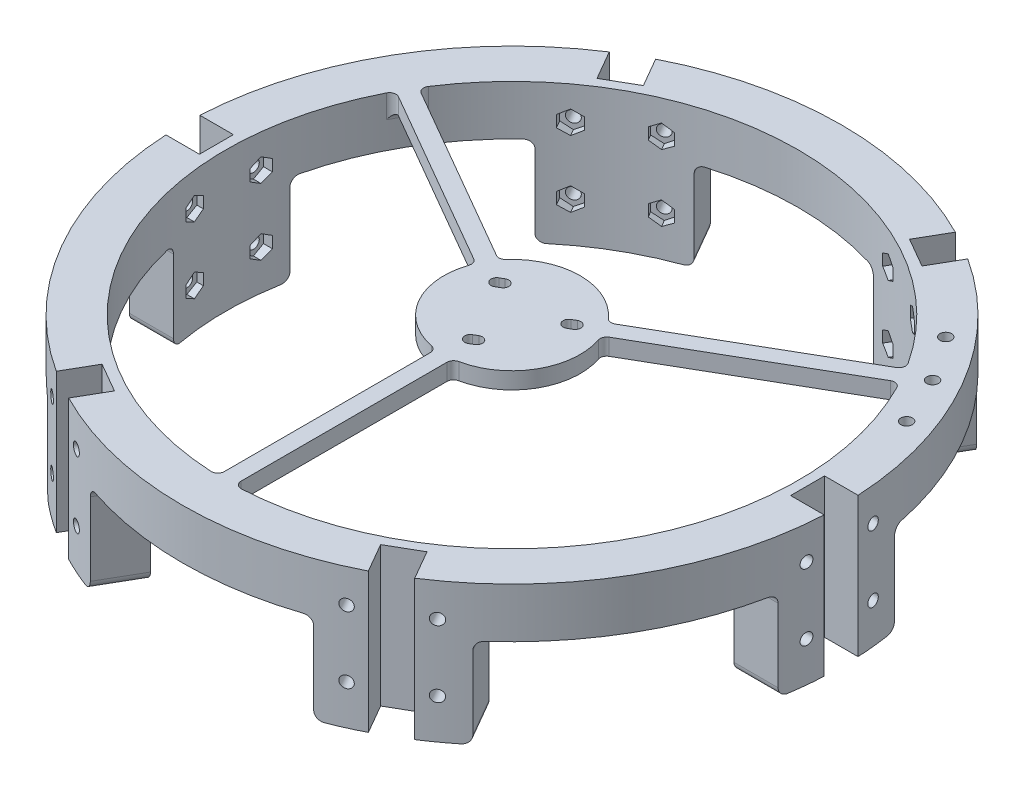
SolidWorks part; units mm, degrees
ref_plane "Спереди" through (0, 0, 0) normal (0, 0, 1) x (1, 0, 0)
ref_plane "Сверху" through (0, 0, 0) normal (0, 1, 0) x (1, 0, 0)
ref_plane "Справа" through (0, 0, 0) normal (1, 0, 0) x (0, 0, -1)
sketch "Эскиз1" plane through (0, 0, 0) normal (0, 1, 0) x (1, 0, 0)
  circle A0 centre (0, 0) radius 99
  dimension "D1" = 198
extrude "Бобышка-Вытянуть1" add sketch "Эскиз1" along normal blind 15
sketch "Эскиз2" plane through (0, 15, 0) normal (0, 1, 0) x (1, 0, 0)
  line L0 (-93.9, 0) -> (0, 0) construction
  line L1 (-99, 5.1) -> (-88.8, 5.1)
  line L2 (-99, 5.1) -> (-99, -5.1)
  line L3 (-99, -5.1) -> (-88.8, -5.1)
  line L4 (-88.8, 5.1) -> (-88.8, -5.1)
  line L5 (-99, 5.1) -> (-88.8, -5.1) construction
  line L6 (-99, -5.1) -> (-88.8, 5.1) construction
  circle A0 centre (0, 0) radius 99 construction
  point P0 (-93.9, 0)
  dimension "D1" = 10.2
  dimension "D2" = 10.2
extrude "Вырез-Вытянуть1" cut sketch "Эскиз2" against normal through all
pattern_circular "Круговой массив1" count 6 over 360 about axis through (0, 15, 0) along (0, 1, 0) of "Вырез-Вытянуть1"
sketch "Эскиз3" plane through (0, 15, 0) normal (0, 1, 0) x (1, 0, 0)
  circle A0 centre (0, 0) radius 86
  point P5 (-86, 0)
  dimension "D1" = 172
extrude "Вырез-Вытянуть2" cut sketch "Эскиз3" against normal through all
ref_plane "Плоскость1" through (0, 0, -99) normal (0, 0, -1) x (-1, 0, 0)
sketch "Эскиз6" plane through (0, 0, -99) normal (0, 0, -1) x (-1, 0, 0)
  line L0 (-45.0175, 0) -> (45.0175, 0) construction
  line L1 (-15, -17.9681) -> (15, -17.9681)
  line L2 (-15, -17.9681) -> (-15, 0)
  line L3 (-15, 0) -> (15, 0)
  line L4 (15, -17.9681) -> (15, 0)
  line L5 (-15, -17.9681) -> (15, 0) construction
  line L6 (-15, 0) -> (15, -17.9681) construction
  line L7 (0, -8.984) -> (0, 0) construction
  point P0 (0, -8.984)
  dimension "D1" = 30
sketch "Эскиз7" plane through (0, 15, 0) normal (0, 1, 0) x (1, 0, 0)
  circle A0 centre (0, 0) radius 99
  arc A1 (45.0175, 88.1727) -> (-45.0175, 88.1727) centre (0, 0) ccw construction
  circle A2 centre (0, 0) radius 104
  point P7 (0, 0)
  dimension "D1" = 5
sketch "Эскиз8" plane through (0, 0, -99) normal (0, 0, -1) x (-1, 0, 0)
  line L0 (0, -8.5) -> (0, 0) construction
  circle A0 centre (0, -8.5) radius 2.5
  dimension "D2" = 5
  dimension "D1" = 8.5
sketch "Эскиз10" plane through (0, 0, 0) normal (0, -1, 0) x (1, 0, 0)
  line L0 (67.0955, -65.2982) -> (88.5621, -32.8102)
  line L1 (88.5621, -32.8102) -> (81.0551, -27.8499)
  line L2 (81.0551, -27.8499) -> (59.5884, -60.3378)
  line L3 (59.5884, -60.3378) -> (67.0955, -65.2982)
extrude "Бобышка-Вытянуть3" add sketch "Эскиз10" along normal blind 500
sketch "Эскиз11" plane through (0, 15, 0) normal (0, 1, 0) x (1, 0, 0)
  line L0 (0, 0) -> (-74.4782, 43) construction
  line L1 (0, 0) -> (74.4782, 43) construction
  line L2 (0, 0) -> (0, -86) construction
  line L9 (-16.371, 12.3386) -> (-73.1967, 45.1469)
  line L10 (18.871, 8.0084) -> (75.6967, 40.8168)
  line L12 (16.371, 12.3386) -> (73.1967, 45.1469)
  line L14 (2.5, -20.347) -> (2.5, -85.9637)
  line L16 (-2.5, -20.347) -> (-2.5, -85.9637)
  line L18 (-18.871, 8.0084) -> (-75.6967, 40.8168)
  arc A0 (2.5, -20.347) -> (18.871, 8.0084) centre (0, 0) ccw
  circle A1 centre (0, 0) radius 86 construction
  circle A2 centre (0, 0) radius 86 construction
  arc A3 (81.3083, 28.0172) -> (60.6093, 61.0124) centre (0, 0) ccw construction
  arc A4 (-75.6967, 40.8168) -> (-73.1967, 45.1469) centre (0, 0) cw
  arc A5 (73.1967, 45.1469) -> (75.6967, 40.8168) centre (0, 0) cw
  arc A6 (2.5, -85.9637) -> (-2.5, -85.9637) centre (0, 0) cw
  arc A7 (-18.871, 8.0084) -> (-2.5, -20.347) centre (0, 0) ccw
  arc A8 (16.371, 12.3386) -> (-16.371, 12.3386) centre (0, 0) ccw
  point P9 (1.25, 2.1651)
  point P11 (1.25, -2.1651)
  point P13 (-2.5, 0)
  point P15 (-1.25, -2.1651)
  point P17 (-1.25, 2.1651)
  point P19 (2.5, 0)
  dimension "D1" = 41
  dimension "D2" = 120
  dimension "D3" = 120
  dimension "D4" = 2.5
  dimension "D5" = 2.5
  dimension "D6" = 2.5
  dimension "D7" = 2.5
  dimension "D8" = 2.5
  dimension "D9" = 2.5
extrude "Бобышка-Вытянуть4" add sketch "Эскиз11" against normal blind 5
sketch "Эскиз12" plane through (0, 10, 0) normal (0, -1, 0) x (1, 0, 0)
  circle A0 centre (0, 0) radius 20.5
fillet "Скругление2" radius 2 15 edges at (-73.1967, 12.5, -45.1469) (-75.6967, 12.5, -40.8168) (73.1967, 12.5, -45.1469) (75.6967, 12.5, -40.8168) (2.5, 12.5, 85.9637) (-2.5, 12.5, 85.9637) (-16.371, 12.5, -12.3386) (-18.871, 12.5, -8.0084) (-2.5, 12.5, 20.347) (2.5, 12.5, 20.347) (18.871, 12.5, -8.0084) (16.371, 12.5, -12.3386) (0, 10, 86) (-74.4782, 10, -43) (74.4782, 10, -43)
sketch "Эскиз13" plane through (0, 15, 0) normal (0, 1, 0) x (1, 0, 0)
  line L0 (0, 0) -> (10.8253, 6.25) construction
  line L1 (0, 0) -> (0, -12.5) construction
  line L2 (0, 0) -> (-10.8253, 6.25) construction
  line L3 (20.3419, 8.8576) -> (73.8917, 39.7746) construction
  line L4 (10.8253, 6.25) -> (12.0378, 6.95) construction
  line L5 (9.9753, 7.7222) -> (11.1878, 8.4222)
  line L6 (11.6753, 4.7778) -> (12.8878, 5.4778)
  line L7 (-10.8253, 6.25) -> (-9.6129, 6.95) construction
  line L8 (-11.6753, 7.7222) -> (-10.4629, 8.4222)
  line L9 (-9.9753, 4.7778) -> (-8.7629, 5.4778)
  line L10 (0, -12.5) -> (1.2124, -11.8) construction
  line L11 (-0.85, -11.0278) -> (0.3624, -10.3278)
  line L12 (0.85, -13.9722) -> (2.0624, -13.2722)
  circle A0 centre (0, 0) radius 12.5 construction
  arc A4 (9.9753, 7.7222) -> (11.6753, 4.7778) centre (10.8253, 6.25) ccw
  arc A5 (12.8878, 5.4778) -> (11.1878, 8.4222) centre (12.0378, 6.95) ccw
  arc A6 (-11.6753, 7.7222) -> (-9.9753, 4.7778) centre (-10.8253, 6.25) ccw
  arc A7 (-8.7629, 5.4778) -> (-10.4629, 8.4222) centre (-9.6129, 6.95) ccw
  arc A8 (-0.85, -11.0278) -> (0.85, -13.9722) centre (0, -12.5) ccw
  arc A9 (2.0624, -13.2722) -> (0.3624, -10.3278) centre (1.2124, -11.8) ccw
  point P8 (11.4315, 6.6)
  point P14 (-10.2191, 6.6)
  point P20 (0.6062, -12.15)
  dimension "D1" = 25
  dimension "D4" = 1.4
  dimension "D5" = 1.4
  dimension "D6" = 1.4
  dimension "D7" = 1.7
  dimension "D8" = 1.7
  dimension "D9" = 1.7
  dimension "D2" = 120
  dimension "D3" = 120
extrude "Вырез-Вытянуть3" cut sketch "Эскиз13" against normal up to next
sketch "Эскиз15" plane through (0, 0, 0) normal (0, -1, 0) x (1, 0, 0)
  line L0 (84.2007, 17.5) -> (97.441, 17.5)
  line L1 (84.2007, -17.5) -> (97.441, -17.5)
  line L2 (90.8208, 0) -> (90.8208, 17.5) construction
  line L3 (90.8208, 0) -> (90.8208, -17.5) construction
  line L4 (90.8208, 0) -> (88.8, 0) construction
  line L5 (88.8, -5.1) -> (88.8, 5.1) construction
  arc A0 (84.2007, 17.5) -> (84.2007, -17.5) centre (0, 0) cw
  arc A1 (97.441, 17.5) -> (97.441, -17.5) centre (0, 0) cw
  circle A2 centre (0, 0) radius 86 construction
  circle A3 centre (0, 0) radius 99 construction
  point P8 (83.6421, -20)
  point P15 (83.6421, 20)
  point P16 (96.8926, 20.3181)
  point P19 (93.888, 0)
  point P20 (0, 0)
  point P21 (96.9588, -20)
  point P22 (94.0348, 0)
  point P23 (94.0348, 20)
  point P24 (90.8208, 17.5)
  point P25 (0, 0)
  dimension "D1" = 35
extrude "Бобышка-Вытянуть5" add sketch "Эскиз15" along normal blind 27
sketch "Эскиз16" plane through (0, 0, 0) normal (0, 1, 0) x (1, 0, 0)
  line L0 (98.8685, 5.1) -> (88.8, 5.1) construction
  line L1 (88.8, -5.1) -> (99.8, -5.1)
  line L2 (88.8, -5.1) -> (88.8, 5.1)
  line L3 (88.8, 5.1) -> (99.8, 5.1)
  line L4 (99.8, -5.1) -> (99.8, 5.1)
  point P6 (0, 0)
  point P7 (89, 5)
  dimension "D1" = 11
extrude "Вырез-Вытянуть5" cut sketch "Эскиз16" against normal through all
ref_plane "Плоскость2" through (98.8685, 0, 0) normal (-1, 0, 0) x (0, 0, 1)
sketch "Эскиз17" plane through (98.8685, 0, 0) normal (-1, 0, 0) x (0, 0, 1)
  line L0 (0, 5) -> (0, 15) construction
  line L1 (-10, -15) -> (10, -15) construction
  line L2 (-10, -15) -> (-10, 5) construction
  line L3 (-10, 5) -> (10, 5) construction
  line L4 (10, -15) -> (10, 5) construction
  line L5 (-10, -15) -> (10, 5) construction
  line L6 (-10, 5) -> (10, -15) construction
  line L7 (104, 15) -> (-104, 15) construction
  circle A0 centre (-10, -15) radius 1.75
  circle A1 centre (10, -15) radius 1.75
  circle A2 centre (10, 5) radius 1.75
  circle A3 centre (-10, 5) radius 1.75
  point P0 (0, -5)
  dimension "D4" = 3.5
  dimension "D5" = 3.5
  dimension "D6" = 3.5
  dimension "D7" = 3.5
  dimension "D1" = 10
  dimension "D2" = 20
  dimension "D3" = 20
extrude "Вырез-Вытянуть6" cut sketch "Эскиз17" along normal up to next
fillet "Скругление3" radius 2.5 4 edges at (90.8208, 0, -17.5) (90.8208, 0, 17.5) (90.8208, -27, 17.5) (90.8208, -27, -17.5)
sketch "Эскиз18" plane through (0, -27, 0) normal (0, -1, 0) x (1, 0, 0)
  line L0 (88.8, 0) -> (84.6818, 15) construction
  line L1 (88.8, -5.1) -> (88.8, 5.1) construction
  line L2 (84.6818, 15) -> (84.6818, -15) construction
  line L3 (84.6818, -15) -> (88.8, 0) construction
ref_plane "Плоскость3" through (84.6818, 0, 0) normal (1, 0, 0) x (0, 0, -1)
sketch "Эскиз19" plane through (84.6818, 0, 0) normal (1, 0, 0) x (0, 0, -1)
  line L1 (-10, 1.5359) -> (-7, 3.2679)
  line L2 (-7, 3.2679) -> (-7, 6.7321)
  line L3 (-7, 6.7321) -> (-10, 8.4641)
  line L4 (-10, 8.4641) -> (-13, 6.7321)
  line L5 (-13, 6.7321) -> (-13, 3.2679)
  line L6 (-13, 3.2679) -> (-10, 1.5359)
  line L7 (10, 1.5359) -> (13, 3.2679)
  line L8 (13, 3.2679) -> (13, 6.7321)
  line L9 (13, 6.7321) -> (10, 8.4641)
  line L10 (10, 8.4641) -> (7, 6.7321)
  line L11 (7, 6.7321) -> (7, 3.2679)
  line L12 (7, 3.2679) -> (10, 1.5359)
  line L13 (10, -18.4641) -> (13, -16.7321)
  line L14 (13, -16.7321) -> (13, -13.2679)
  line L15 (13, -13.2679) -> (10, -11.5359)
  line L16 (10, -11.5359) -> (7, -13.2679)
  line L17 (7, -13.2679) -> (7, -16.7321)
  line L18 (7, -16.7321) -> (10, -18.4641)
  line L19 (-10, -18.4641) -> (-7, -16.7321)
  line L20 (-7, -16.7321) -> (-7, -13.2679)
  line L21 (-7, -13.2679) -> (-10, -11.5359)
  line L22 (-10, -11.5359) -> (-13, -13.2679)
  line L23 (-13, -13.2679) -> (-13, -16.7321)
  line L24 (-13, -16.7321) -> (-10, -18.4641)
  circle A0 centre (-10, 5) radius 3 construction
  circle A1 centre (10, 5) radius 3 construction
  circle A2 centre (10, -15) radius 3 construction
  circle A3 centre (-10, -15) radius 3 construction
  dimension "D1" = 6
  dimension "D2" = 6
  dimension "D3" = 6
  dimension "D4" = 6
extrude "Вырез-Вытянуть7" cut sketch "Эскиз19" along normal blind 3 and the other way blind 1
pattern_circular "Круговой массив2" count 6 over 360 about axis through (0, 0, 0) along (0, 1, 0) of "Вырез-Вытянуть6", "Скругление3", "Вырез-Вытянуть7", "Бобышка-Вытянуть5", "Круговой массив1", "Вырез-Вытянуть5"
sketch "Эскиз20" plane through (0, -500, 0) normal (0, -1, 0) x (1, 0, 0)
  line L0 (81.0551, -27.8499) -> (59.5884, -60.3378)
  line L1 (59.5884, -60.3378) -> (67.0955, -65.2982)
  line L2 (67.0955, -65.2982) -> (88.5621, -32.8102)
  line L3 (88.5621, -32.8102) -> (81.0551, -27.8499)
extrude "Вырез-Вытянуть8" cut sketch "Эскиз20" against normal up to surface (500 mm away) up to face at (75.947, 0, -45.7614)
sketch "Эскиз21" plane through (0, 0, 0) normal (0, -1, 0) x (1, 0, 0)
  line L0 (0, 0) -> (80.1073, -46.25) construction
  line L1 (71.3917, -44.1048) -> (17.8419, -13.1878) construction
  line L2 (0, 0) -> (70.8591, -59.4579) construction
  line L3 (0, 0) -> (86.9216, -31.6369) construction
  circle A0 centre (0, 0) radius 92.5 construction
  arc A1 (59.1416, -62.4362) -> (83.6421, -20) centre (0, 0) ccw construction
  circle A2 centre (80.1073, -46.25) radius 1.75
  circle A3 centre (86.9216, -31.6369) radius 1.75
  circle A4 centre (70.8591, -59.4579) radius 1.75
  dimension "D1" = 6.5
  dimension "D4" = 3.5
  dimension "D5" = 3.5
  dimension "D6" = 3.5
  dimension "D2" = 20
  dimension "D3" = 10
extrude "Вырез-Вытянуть9" cut sketch "Эскиз21" against normal through all
